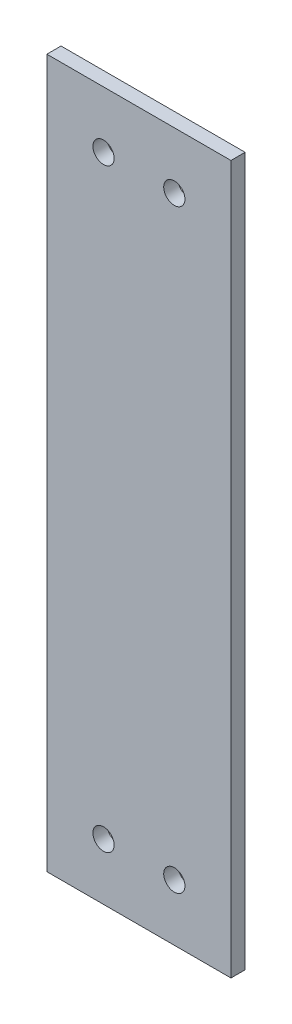
SolidWorks part; units mm, degrees
ref_plane "Спереди" through (0, 0, 0) normal (0, 0, 1) x (1, 0, 0)
ref_plane "Сверху" through (0, 0, 0) normal (0, 1, 0) x (1, 0, 0)
ref_plane "Справа" through (0, 0, 0) normal (1, 0, 0) x (0, 0, -1)
sketch "Эскиз1" plane through (0, 0, 0) normal (0, 0, 1) x (1, 0, 0)
  line L1 (0, 0) -> (26, 0)
  line L2 (0, 0) -> (0, 100)
  line L3 (0, 100) -> (26, 100)
  line L4 (26, 0) -> (26, 100)
  circle A0 centre (8, 8) radius 1.5
  circle A1 centre (18, 8) radius 1.5
  circle A2 centre (18, 92) radius 1.5
  circle A3 centre (8, 92) radius 1.5
  dimension "D3" = 3
  dimension "D1" = 100
  dimension "D2" = 10
  dimension "D4" = 8
  dimension "D5" = 8
  dimension "D8" = 8
  dimension "D9" = 8
  dimension "D10" = 8
  dimension "D7" = 2
  dimension "D6" = 2
extrude "Бобышка-Вытянуть1" add sketch "Эскиз1" along normal blind 2
